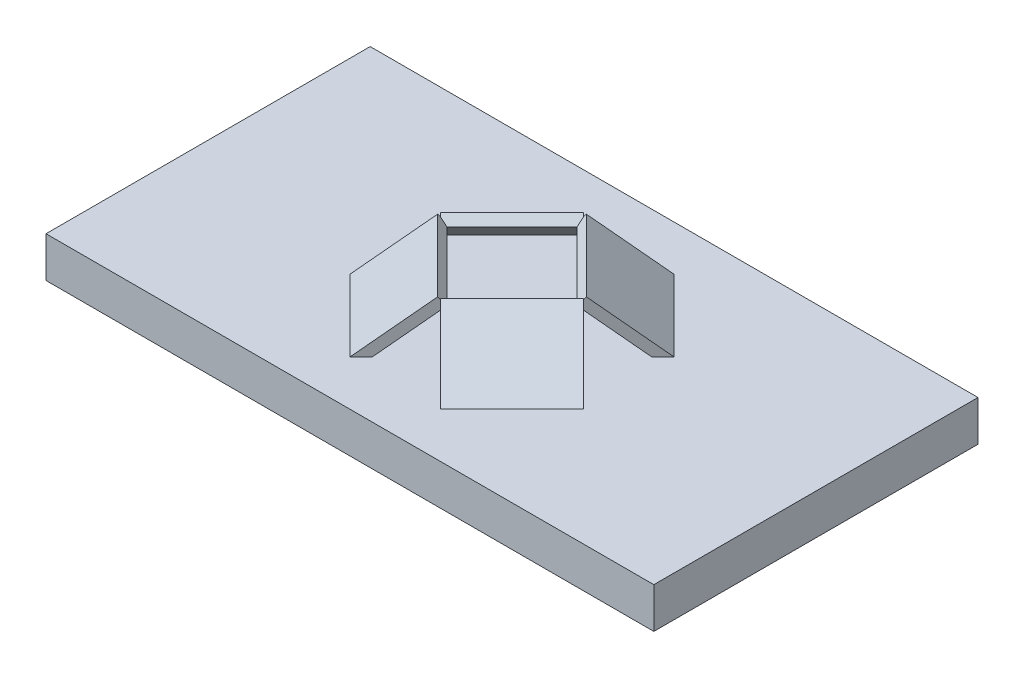
SolidWorks part; units mm, degrees
ref_plane "Front Plane" through (0, 0, 0) normal (0, 0, 1) x (1, 0, 0)
ref_plane "Top Plane" through (0, 0, 0) normal (0, 1, 0) x (1, 0, 0)
ref_plane "Right Plane" through (0, 0, 0) normal (1, 0, 0) x (0, 0, -1)
sketch "Sketch1" plane through (0, 0, 0) normal (0, 1, 0) x (1, 0, 0)
  line L1 (-15, -8) -> (15, -8)
  line L2 (-15, -8) -> (-15, 8)
  line L3 (-15, 8) -> (15, 8)
  line L4 (15, -8) -> (15, 8)
  line L5 (-15, -8) -> (15, 8) construction
  line L6 (-15, 8) -> (15, -8) construction
  point P0 (0, 0)
  dimension "D1" = 30
  dimension "D2" = 16
extrude "Boss-Extrude1" add sketch "Sketch1" along normal blind 2 contours L2 L3 L4 L1
sketch "Sketch2" plane through (0, 2, 0) normal (0, 1, 0) x (1, 0, 0)
  line L0 (0, 8) -> (-8, 0) construction
  line L2 (-15, 8) -> (15, 8) construction
  line L3 (-8, 0) -> (0, -8) construction
  line L4 (-15, -8) -> (15, -8) construction
  line L5 (0, -8) -> (8, 0) construction
  line L6 (8, 0) -> (0, 8) construction
ref_plane "Plane1" through (-4, 0, 4) normal (-0.7071, 0, 0.7071) x (0.7071, 0, 0.7071)
ref_plane "Plane2" through (-2.3491, 3.9591, 2.3491) normal (0.4545, -0.766, -0.4545) x (0.7071, 0, 0.7071)
sketch "Sketch4" plane through (-2.3491, 3.9591, 2.3491) normal (0.4545, -0.766, -0.4545) x (0.7071, 0, 0.7071)
  line L0 (-5.6569, 3.0478) -> (5.6569, 3.0478) construction
  line L1 (2.5, 3.0478) -> (-2.5, 3.0478)
  line L2 (2.5, 3.0478) -> (2.5, -0.9522)
  line L3 (2.5, -0.9522) -> (-2.5, -0.9522)
  line L4 (-2.5, 3.0478) -> (-2.5, -0.9522)
  point P6 (0, 3.0478)
  point P7 (0, 3.0478)
  dimension "D1" = 5
  dimension "D2" = 4
extrude "Boss-Extrude2" add sketch "Sketch4" along normal blind 0.5
ref_axis "Axis1" through (0, 0, 0) along (0, 1, 0)
pattern_circular "CirPattern1" count 4 over 360 about axis through (0, 0, 0) along (0, 1, 0) of "Boss-Extrude2"
